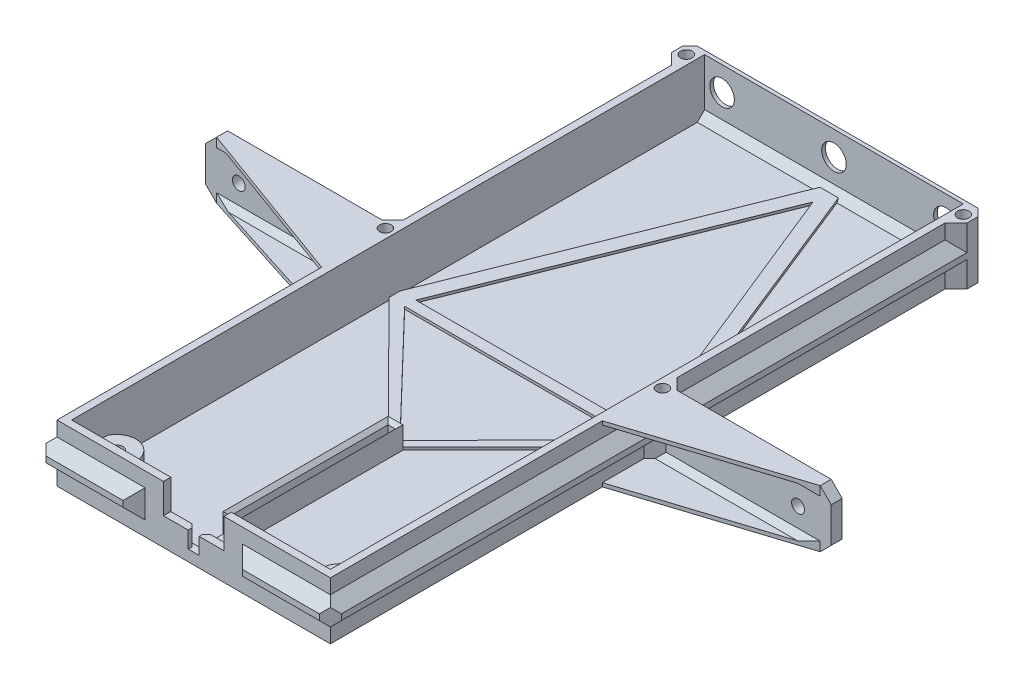
SolidWorks part; units mm, degrees
ref_plane "Front Plane" through (0, 0, 0) normal (0, 0, 1) x (1, 0, 0)
ref_plane "Top Plane" through (0, 0, 0) normal (0, 1, 0) x (1, 0, 0)
ref_plane "Right Plane" through (0, 0, 0) normal (1, 0, 0) x (0, 0, -1)
sketch "Sketch1" plane through (0, 0, 0) normal (0, 1, 0) x (1, 0, 0)
  line L1 (-37.25, 88.25) -> (37.25, 88.25)
  line L2 (-37.25, 88.25) -> (-37.25, -88.25)
  line L3 (-37.25, -88.25) -> (37.25, -88.25)
  line L4 (37.25, 88.25) -> (37.25, -88.25)
  line L5 (-37.25, 88.25) -> (37.25, -88.25) construction
  line L6 (-37.25, -88.25) -> (37.25, 88.25) construction
  point P0 (0, 0)
  dimension "D1" = 74.5
  dimension "D2" = 176.5
extrude "Boss-Extrude1" add sketch "Sketch1" along normal blind 0.6
sketch "Sketch2" plane through (0, 0.6, 0) normal (0, 1, 0) x (1, 0, 0)
  line L0 (37.25, -88.25) -> (37.25, 88.25) construction
  line L1 (-37.25, 88.25) -> (37.25, 88.25)
  line L2 (-37.25, 88.25) -> (-37.25, 82.7452)
  line L3 (-35.25, 86.25) -> (35.25, 86.25)
  line L4 (37.25, 88.25) -> (37.25, 82.7452)
  line L6 (-37.25, -88.25) -> (37.25, -88.25)
  line L7 (-37.25, -88.25) -> (-37.25, -79.7345)
  line L8 (-35.25, -86.25) -> (35.25, -86.25)
  line L9 (37.25, -88.25) -> (37.25, -79.7345)
  line L11 (37.25, -79.7345) -> (37.25, 82.7452)
  line L13 (35.25, -86.25) -> (35.25, 86.25)
  line L15 (-35.25, 86.25) -> (-35.25, -86.25)
  line L17 (-37.25, 82.7452) -> (-37.25, -79.7345)
  dimension "D1" = 2
  dimension "D2" = 2
  dimension "D3" = 2
  dimension "D4" = 2
extrude "Boss-Extrude2" add sketch "Sketch2" along normal blind 15
sketch "Sketch3" plane through (0, 0, -88.25) normal (0, 0, -1) x (-1, 0, 0)
  line L0 (-37.25, 0) -> (37.25, 0) construction
  line L1 (-37.25, 15.6) -> (-37.25, 0) construction
  line L2 (37.25, 15.6) -> (37.25, 0) construction
  circle A0 centre (-30.5, 9) radius 3.35
  circle A1 centre (0, 9) radius 3.35
  circle A2 centre (30.5, 9) radius 3.35
  point P13 (37.25, 7.8)
  dimension "D1" = 6.7
  dimension "D2" = 6.7
  dimension "D3" = 6.7
  dimension "D4" = 9
  dimension "D5" = 9
  dimension "D6" = 9
  dimension "D7" = 0
  dimension "D8" = 6.75
  dimension "D9" = 6.75
extrude "Cut-Extrude2" cut sketch "Sketch3" against normal blind 19
sketch "Sketch5" plane through (0, 0.6, 0) normal (0, 1, 0) x (1, 0, 0)
  line L0 (-35.25, 86.25) -> (-35.25, -86.25) construction
  line L1 (35.25, -86.25) -> (35.25, 86.25) construction
  line L2 (-35.25, -86.25) -> (35.25, -86.25) construction
  circle A0 centre (-30.5, -78.75) radius 1.75
  circle A1 centre (30.5, -78.75) radius 1.75
  dimension "D1" = 3.5
  dimension "D2" = 3.5
  dimension "D3" = 4.75
  dimension "D4" = 4.75
  dimension "D5" = 7.5
  dimension "D6" = 7.5
extrude "Cut-Extrude3" cut sketch "Sketch5" against normal blind 19
sketch "Sketch6" plane through (0, 0.6, 0) normal (0, 1, 0) x (1, 0, 0)
  circle A0 centre (-30.5, -78.75) radius 5.25
  circle A1 centre (30.5, -78.75) radius 5.25
  circle A2 centre (-30.5, -78.75) radius 1.75
  circle A3 centre (30.5, -78.75) radius 1.75
  dimension "D1" = 3.5
  dimension "D2" = 3.5
extrude "Boss-Extrude4" add sketch "Sketch6" along normal blind 6.5
sketch "Sketch7" plane through (0, 0, 88.25) normal (0, 0, 1) x (1, 0, 0)
  line L0 (-37.25, 15.6) -> (37.25, 15.6) construction
  line L1 (-8.25, 7.5) -> (8.25, 7.5)
  line L2 (-8.25, 7.5) -> (-8.25, 15.6)
  line L3 (-8.25, 15.6) -> (8.25, 15.6)
  line L4 (8.25, 7.5) -> (8.25, 15.6)
  line L5 (-37.25, 0) -> (37.25, 0) construction
  dimension "D1" = 16.5
  dimension "D2" = 8.25
  dimension "D3" = 7.5
extrude "Cut-Extrude4" cut sketch "Sketch7" against normal blind 6
sketch "Sketch8" plane through (0, 0, 88.25) normal (0, 0, 1) x (1, 0, 0)
  line L0 (-8.25, 7.5) -> (8.25, 7.5) construction
  line L1 (-1.5, 7.5) -> (1.5, 7.5)
  line L2 (-1.5, 7.5) -> (-1.5, 3)
  line L3 (-1.5, 3) -> (1.5, 3)
  line L4 (1.5, 7.5) -> (1.5, 3)
  dimension "D1" = 3
  dimension "D2" = 1.5
  dimension "D3" = 4.5
extrude "Cut-Extrude5" cut sketch "Sketch8" against normal blind 6
sketch "Sketch9" plane through (0, 0.6, 0) normal (0, 1, 0) x (1, 0, 0)
  line L0 (1.5, -86.25) -> (1.5, -88.25) construction
  line L1 (-1, -77.25) -> (1, -77.25)
  line L2 (-1, -77.25) -> (-1, -34.25)
  line L3 (-1, -34.25) -> (1, -34.25)
  line L4 (1, -77.25) -> (1, -34.25)
  line L5 (-35.25, -86.25) -> (35.25, -86.25) construction
  point P6 (1.5, -87.25)
  dimension "D1" = 2
  dimension "D2" = 0.5
  dimension "D3" = 9
  dimension "D4" = 43
extrude "Cut-Extrude6" cut sketch "Sketch9" against normal blind 6
sketch "Sketch10" plane through (0, 0.6, 0) normal (0, 1, 0) x (1, 0, 0)
  line L1 (-1, -34.25) -> (1, -34.25)
  line L2 (-1, -34.25) -> (-1, -77.25)
  line L3 (-1, -77.25) -> (1, -77.25)
  line L4 (1, -34.25) -> (1, -77.25)
  line L5 (-2, -33.25) -> (2, -33.25)
  line L6 (-2, -33.25) -> (-2, -78.25)
  line L7 (-2, -78.25) -> (2, -78.25)
  line L8 (2, -33.25) -> (2, -78.25)
  dimension "D1" = 1
  dimension "D2" = 1
  dimension "D3" = 1
  dimension "D4" = 1
extrude "Boss-Extrude5" add sketch "Sketch10" along normal blind 6
chamfer "Chamfer1" distance 1 angle 45 4 edges at (0, 6.6, 77.25) (-1, 6.6, 55.75) (0, 6.6, 34.25) (1, 6.6, 55.75)
chamfer "Chamfer4" distance 1 angle 45 2 edges at (-1.5, 5.25, 86.25) (1.5, 5.25, 86.25)
sketch "Sketch11" plane through (0, 0, 0) normal (0, -1, 0) x (1, 0, 0)
  line L1 (-37.25, -88.25) -> (-37.25, 88.25) construction
  line L2 (-37.25, -0.25) -> (-85.25, -0.25)
  line L3 (-37.25, -0.25) -> (-37.25, -3.25)
  line L4 (-37.25, -3.25) -> (-85.25, -3.25)
  line L5 (37.25, 88.25) -> (37.25, -88.25) construction
  line L6 (37.25, -0.25) -> (85.25, -0.25)
  line L7 (37.25, -0.25) -> (37.25, -3.25)
  line L8 (37.25, -3.25) -> (85.25, -3.25)
  line L9 (85.25, -0.25) -> (85.25, -3.25)
  line L10 (-85.25, -0.25) -> (-85.25, -3.25)
  line L11 (37.25, -88.25) -> (-37.25, -88.25) construction
  dimension "D1" = 3
  dimension "D2" = 3
  dimension "D3" = 85
  dimension "D4" = 85
  dimension "D5" = 48
  dimension "D6" = 48
extrude "Boss-Extrude6" add sketch "Sketch11" against normal blind 15.6
sketch "Sketch12" plane through (0, 0, -0.25) normal (0, 0, 1) x (1, 0, 0)
  line L1 (85.25, 15.6) -> (85.25, 0) construction
  circle A0 centre (-76.2, 7.75) radius 1.75
  circle A1 centre (76.2, 7.75) radius 1.75
  dimension "D1" = 3.5
  dimension "D2" = 3.5
  dimension "D3" = 152.4
  dimension "D4" = 9.05
extrude "Cut-Extrude7" cut sketch "Sketch12" against normal blind 15.5
chamfer "Chamfer5" distance 3 angle 45 4 edges at (85.25, 0, -1.75) (85.25, 15.6, -1.75) (-85.25, 15.6, -1.75) (-85.25, 0, -1.75)
chamfer "Chamfer6" distance 3 angle 45 4 edges at (37.25, 7.8, -3.25) (37.25, 7.8, -0.25) (-37.25, 7.8, -0.25) (-37.25, 7.8, -3.25)
sketch "Sketch13" plane through (0, 15.6, 0) normal (0, 1, 0) x (1, 0, 0)
  line L0 (35.25, -76.5139) -> (35.25, 86.25) construction
  line L1 (-35.25, 86.25) -> (-35.25, -86.25) construction
  line L2 (-40.25, 0.25) -> (-82.25, 0.25) construction
  line L3 (82.25, 0.25) -> (40.25, 0.25) construction
  circle A0 centre (-37.75, 1.75) radius 1.6
  circle A1 centre (37.75, 1.75) radius 1.6
  dimension "D1" = 3.2
  dimension "D2" = 3.2
  dimension "D3" = 2.5
  dimension "D4" = 2.5
  dimension "D5" = 1.5
  dimension "D6" = 1.5
extrude "Cut-Extrude8" cut sketch "Sketch13" against normal blind 25.5
sketch "Sketch14" plane through (0, 0, 0) normal (0, -1, 0) x (1, 0, 0)
  line L0 (-37.25, -88.25) -> (-40.25, -85.25)
  line L1 (-40.25, -85.25) -> (-40.25, -82.25)
  line L2 (-40.25, -82.25) -> (-37.25, -79.25)
  line L3 (-37.25, -88.25) -> (-37.25, -6.25) construction
  line L4 (-37.25, -79.25) -> (-37.25, -88.25)
  line L5 (37.25, -88.25) -> (40.25, -85.25)
  line L6 (40.25, -85.25) -> (40.25, -82.25)
  line L7 (40.25, -82.25) -> (37.25, -79.25)
  line L8 (37.25, -6.25) -> (37.25, -88.25) construction
  line L9 (37.25, -79.25) -> (37.25, -88.25)
  dimension "D1" = 3
  dimension "D2" = 3
extrude "Boss-Extrude7" add sketch "Sketch14" against normal blind 15.6
sketch "Sketch15" plane through (0, 15.6, 0) normal (0, 1, 0) x (1, 0, 0)
  line L0 (35.25, -86.25) -> (35.25, 86.25) construction
  line L1 (-35.25, 86.25) -> (-35.25, -86.25) construction
  circle A0 centre (37.75, 83.75) radius 1.6
  circle A1 centre (-37.75, 83.75) radius 1.6
  dimension "D1" = 3.2
  dimension "D2" = 2.5
  dimension "D3" = 3.2
  dimension "D4" = 2.5
extrude "Cut-Extrude9" cut sketch "Sketch15" against normal blind 15.6
sketch "Sketch16" plane through (37.25, 0, 0) normal (1, 0, 0) x (0, 0, -1)
  line L1 (-88.25, 15.6) -> (-88.25, 0) construction
  line L2 (-88.25, 8.6) -> (0.25, 8.6)
  line L3 (-88.25, 8.6) -> (-88.25, 7)
  line L4 (-88.25, 7) -> (0.25, 7)
  line L9 (3.25, 0) -> (3.25, 15.6) construction
  line L10 (3.25, 8.6) -> (82.25, 8.6)
  line L11 (3.25, 8.6) -> (3.25, 7)
  line L12 (3.25, 7) -> (82.25, 7)
  line L14 (0.25, 8.6) -> (0.25, 7)
  line L15 (0.25, 12.6) -> (0.25, 3) construction
  line L16 (82.25, 8.6) -> (82.25, 7)
  line L17 (82.25, 15.6) -> (82.25, 0) construction
extrude "Boss-Extrude8" add sketch "Sketch16" along normal blind 3
chamfer "Chamfer7" distance 3 angle 45 4 edges at (37.25, 8.6, -42.75) (37.25, 7, -42.75) (37.25, 7, 45.5) (37.25, 8.6, 45.5)
sketch "Sketch17" plane through (-37.25, 0, 0) normal (-1, 0, 0) x (0, 0, 1)
  line L0 (-82.25, 15.6) -> (-82.25, 0) construction
  line L1 (-82.25, 8.6) -> (-3.25, 8.6)
  line L2 (-82.25, 8.6) -> (-82.25, 7)
  line L3 (-82.25, 7) -> (-3.25, 7)
  line L4 (-3.25, 8.6) -> (-3.25, 7)
  line L5 (-3.25, 15.6) -> (-3.25, 0) construction
  line L6 (-79.25, 15.6) -> (-6.25, 15.6) construction
  line L7 (-79.25, 0) -> (-6.25, 0) construction
  line L8 (-0.25, 12.6) -> (-0.25, 3) construction
  line L9 (-0.25, 8.6) -> (88.25, 8.6)
  line L10 (-0.25, 8.6) -> (-0.25, 7)
  line L11 (-0.25, 7) -> (88.25, 7)
  line L12 (88.25, 8.6) -> (88.25, 7)
  dimension "D1" = 7
  dimension "D2" = 7
extrude "Boss-Extrude9" add sketch "Sketch17" along normal blind 3
chamfer "Chamfer8" distance 3 angle 45 4 edges at (-37.25, 8.6, 45.5) (-37.25, 7, 45.5) (-37.25, 7, -42.75) (-37.25, 8.6, -42.75)
sketch "Sketch18" plane through (0, 0, 88.25) normal (0, 0, 1) x (1, 0, 0)
  line L0 (-8.25, 15.6) -> (-8.25, 7.5) construction
  line L1 (-40.25, 8.6) -> (-16.25, 8.6)
  line L2 (-40.25, 8.6) -> (-40.25, 7)
  line L3 (-40.25, 7) -> (-16.25, 7)
  line L4 (-16.25, 8.6) -> (-16.25, 7)
  line L5 (40.25, 8.6) -> (16.25, 8.6)
  line L6 (40.25, 8.6) -> (40.25, 7)
  line L7 (40.25, 7) -> (16.25, 7)
  line L8 (16.25, 8.6) -> (16.25, 7)
  line L9 (8.25, 7.5) -> (8.25, 15.6) construction
  dimension "D1" = 8
  dimension "D2" = 8
extrude "Boss-Extrude10" add sketch "Sketch18" along normal blind 3
chamfer "Chamfer9" distance 3 angle 45 4 edges at (28.25, 8.6, 88.25) (28.25, 7, 88.25) (-28.25, 7, 88.25) (-28.25, 8.6, 88.25)
chamfer "Chamfer10" distance 3 angle 45 2 edges at (40.25, 7.8, 91.25) (-40.25, 7.8, 91.25)
chamfer "Chamfer11" distance 3 angle 45 2 edges at (16.25, 7.8, 88.25) (-16.25, 7.8, 88.25)
sketch "Sketch21" plane through (0, 15.6, 0) normal (0, 1, 0) x (1, 0, 0)
  line L0 (-82.25, 0.25) -> (-37.25, -16.1287)
  line L1 (-37.25, -2.75) -> (-37.25, -88.25) construction
  line L2 (-37.25, -16.1287) -> (-37.25, -2.75)
  line L3 (-37.25, -2.75) -> (-40.25, 0.25)
  line L4 (-40.25, 0.25) -> (-82.25, 0.25)
  line L5 (82.25, 0.25) -> (37.25, -14.1287)
  line L6 (37.25, -88.25) -> (37.25, -2.75) construction
  line L7 (37.25, -14.1287) -> (37.25, -2.75)
  line L8 (37.25, -2.75) -> (40.25, 0.25)
  line L9 (40.25, 0.25) -> (82.25, 0.25)
  dimension "D1" = 20
extrude "Boss-Extrude13" add sketch "Sketch21" against normal blind 1
sketch "Sketch22" plane through (0, 0, 0) normal (0, -1, 0) x (1, 0, 0)
  line L0 (-82.25, -0.25) -> (-37.25, 14.1287)
  line L1 (-37.25, 2.75) -> (-37.25, 88.25) construction
  line L2 (-37.25, 88.25) -> (-37.25, 2.75) construction
  line L3 (-37.25, 14.1287) -> (-37.25, 2.75)
  line L4 (-37.25, 2.75) -> (-40.25, -0.25)
  line L5 (-40.25, -0.25) -> (-82.25, -0.25)
  line L6 (37.25, 14.1287) -> (82.25, -0.25)
  line L7 (37.25, 2.75) -> (37.25, 88.25) construction
  line L8 (37.25, 88.25) -> (37.25, 2.75) construction
  line L9 (82.25, -0.25) -> (40.25, -0.25)
  line L10 (40.25, -0.25) -> (37.25, 2.75)
  line L11 (37.25, 2.75) -> (37.25, 14.1287)
extrude "Boss-Extrude14" add sketch "Sketch22" against normal blind 1
chamfer "Chamfer12" distance 1.5 angle 45 4 edges at (61.25, 14.6, -0.25) (61.25, 1, -0.25) (-61.25, 1, -0.25) (-61.25, 14.6, -0.25)
sketch "Sketch23" plane through (0, 0.6, 0) normal (0, 1, 0) x (1, 0, 0)
  line L0 (-35.25, 86.25) -> (-35.25, -86.25) construction
  line L1 (-30.9535, 3.25) -> (31.25, 3.25)
  line L2 (-35.25, 3.25) -> (-35.25, 0.25)
  line L3 (-31.0152, 0.25) -> (32.0507, 0.25)
  line L4 (35.25, 3.25) -> (35.25, 0.25)
  line L5 (35.25, -86.25) -> (35.25, 86.25) construction
  line L6 (-82.25, 3.25) -> (-40.25, 3.25) construction
  line L7 (-35.25, 0.25) -> (-2, -33.25)
  line L8 (-2, -33.25) -> (2, -33.25)
  line L9 (2, -33.25) -> (35.25, 0.25)
  line L10 (0, -32.0417) -> (32.0507, 0.25)
  line L11 (0, -32.0417) -> (-31.0152, 0.25)
  line L12 (2.5, -86.25) -> (-2.5, -86.25) construction
  line L13 (-2, -78.25) -> (2, -78.25)
  line L14 (-2, -78.25) -> (-2, -86.25)
  line L15 (-2, -86.25) -> (2, -86.25)
  line L16 (2, -78.25) -> (2, -86.25)
  line L17 (-35.25, 3.25) -> (-2, 86.25)
  line L19 (35.25, 86.25) -> (-35.25, 86.25) construction
  line L20 (-2, 86.25) -> (2, 86.25)
  line L21 (2, 86.25) -> (35.25, 3.25)
  line L22 (-30.9535, 3.25) -> (0, 80.5173)
  line L23 (0, 80.5173) -> (31.25, 3.25)
  point P34 (14.5487, -28.4901)
  dimension "D1" = 3
  dimension "D2" = 0
  dimension "D3" = 2
  dimension "D4" = 2
  dimension "D5" = 0
  dimension "D6" = 0
  dimension "D7" = 0
  dimension "D8" = 0
  dimension "D9" = 0
  dimension "D10" = 0
extrude "Boss-Extrude17" add sketch "Sketch23" along normal blind 0.7
sketch "Sketch24" plane through (0, 15.6, 0) normal (0, 1, 0) x (1, 0, 0)
  line L0 (-2, 86.25) -> (-35.25, 86.25) construction
  line L1 (-40.7476, 89.7113) -> (40.5031, 89.7113)
  line L2 (-40.7476, 89.7113) -> (-40.7476, 87.25)
  line L3 (-40.7476, 87.25) -> (40.5031, 87.25)
  line L4 (40.5031, 89.7113) -> (40.5031, 87.25)
  dimension "D1" = 1
extrude "Cut-Extrude10" cut sketch "Sketch24" against normal blind 20
chamfer "Chamfer13" distance 2 angle 45 1 edges at (-18.625, 0.6, -86.25)
